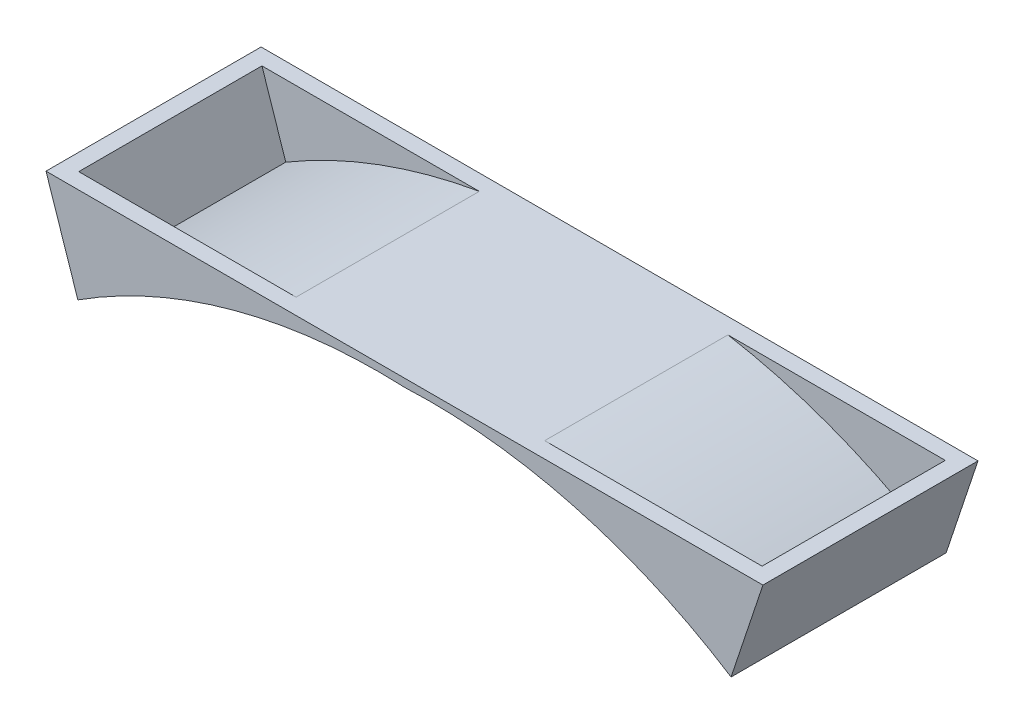
SolidWorks part; units mm, degrees
ref_plane "Front Plane" through (0, 0, 0) normal (0, 0, 1) x (1, 0, 0)
ref_plane "Top Plane" through (0, 0, 0) normal (0, 1, 0) x (1, 0, 0)
ref_plane "Right Plane" through (0, 0, 0) normal (1, 0, 0) x (0, 0, -1)
sketch "Sketch1" plane through (0, 0, 0) normal (0, 0, 1) x (1, 0, 0)
  line L0 (0, 33.4784) -> (0, -30.8107) construction
  line L3 (45, 0) -> (-45, 0)
  line L4 (-45, 0) -> (-41, -12)
  line L5 (45, 0) -> (41, -12)
  arc A0 (-41, -12) -> (0, -1) centre (-3.2149, -70.9261) cw
  arc A1 (41, -12) -> (0, -1) centre (3.2149, -70.9261) ccw
  point P8 (0, 0)
  point P9 (0, 0)
  point P10 (0, 0)
  point P11 (0, 17.044)
  point P12 (0, 0)
  point P13 (0, 0)
  point P17 (0, 0)
  dimension "D5" = 70
  dimension "D1" = 45
  dimension "D2" = 12
  dimension "D3" = 1
  dimension "D4" = 41
extrude "Boss-Extrude1" add sketch "Sketch1" along normal blind 27
shell "Shell1" thickness 2 removed face at (0, 0, 13.5)
